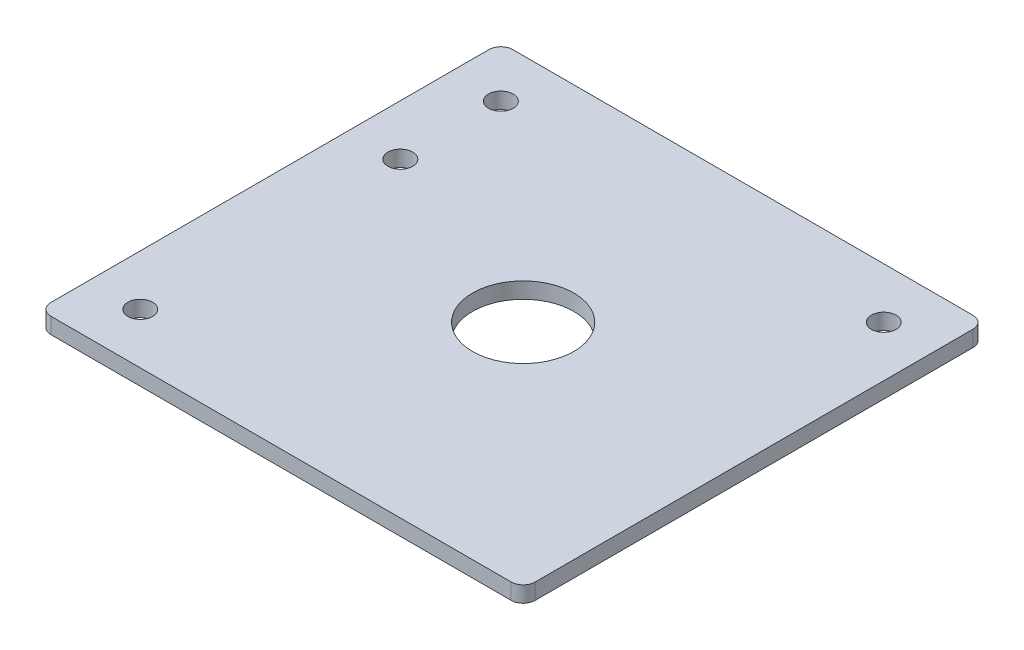
SolidWorks part; units mm, degrees
ref_plane "Front Plane" through (0, 0, 0) normal (0, 0, 1) x (1, 0, 0)
ref_plane "Top Plane" through (0, 0, 0) normal (0, 1, 0) x (1, 0, 0)
ref_plane "Right Plane" through (0, 0, 0) normal (1, 0, 0) x (0, 0, -1)
sketch "Sketch1" plane through (0, 0, 0) normal (0, 1, 0) x (1, 0, 0)
  line L0 (0.7175, -90.4) -> (88.7175, -90.4) construction
  line L1 (0.7175, 0) -> (122.1175, 0)
  line L3 (0.7175, -115.8) -> (122.1175, -115.8)
  line L4 (122.1175, 0) -> (122.1175, -115.8)
  line L5 (-27.2825, -90.4) -> (88.7175, -90.4) construction
  line L6 (88.7175, -90.4) -> (96.7175, -82.4) construction
  line L7 (96.7175, -82.4) -> (96.7175, -33.4) construction
  line L12 (96.7175, -33.4) -> (88.7175, -25.4) construction
  line L13 (88.7175, -25.4) -> (0.7175, -25.4) construction
  line L14 (88.7175, -25.4) -> (-27.2825, -25.4) construction
  line L16 (13.4175, -12.7) -> (0.7175, -12.7) construction
  line L17 (13.4175, -12.7) -> (13.4175, 0) construction
  line L18 (109.4175, -12.7) -> (109.4175, 0) construction
  line L19 (109.4175, -12.7) -> (122.1175, -12.7) construction
  line L20 (13.4175, -103.1) -> (0.7175, -103.1) construction
  line L21 (13.4175, -103.1) -> (13.4175, -100) construction
  line L22 (13.4175, -103.1) -> (13.4175, -115.8) construction
  line L23 (13.4175, -12.7) -> (16.5175, -12.7) construction
  line L24 (0.7175, -35.9) -> (16.9175, -35.9) construction
  line L25 (109.4175, -12.7) -> (109.4175, -15.8) construction
  line L30 (0.7175, 0) -> (0.7175, -115.8)
  line L31 (16.9175, -35.9) -> (-25.2825, -35.9) construction
  line L32 (13.4175, -37.9) -> (16.5175, -37.9) construction
  line L35 (-25.2825, -39.9) -> (16.9175, -39.9) construction
  line L36 (0.7175, -39.9) -> (16.9175, -39.9) construction
  line L37 (13.4175, -35.9) -> (13.4175, -39.9) construction
  line L38 (13.4175, -37.9) -> (0.7175, -37.9) construction
  circle A0 centre (64.2175, -57.9) radius 12.7
  circle A1 centre (13.4175, -12.7) radius 3.1
  circle A2 centre (109.4175, -12.7) radius 3.1
  circle A4 centre (13.4175, -103.1) radius 3.1
  arc A5 (16.9175, -39.9) -> (16.9175, -35.9) centre (16.9175, -37.9) ccw construction
  circle A6 centre (13.4175, -37.9) radius 3.1
  point P38 (13.4175, -37.9)
  dimension "D4" = 25.4
  dimension "D5" = 88
  dimension "D6" = 6.2
  dimension "D1" = 25.4
  dimension "D2" = 25.4
  dimension "D3" = 25.4
  dimension "D7" = 12.7
extrude "Boss-Extrude1" add sketch "Sketch1" along normal blind 4
fillet "Fillet1" radius 3 4 edges at (122.1175, 2, 0) (122.1175, 2, 115.8) (0.7175, 2, 115.8) (0.7175, 2, 0)
